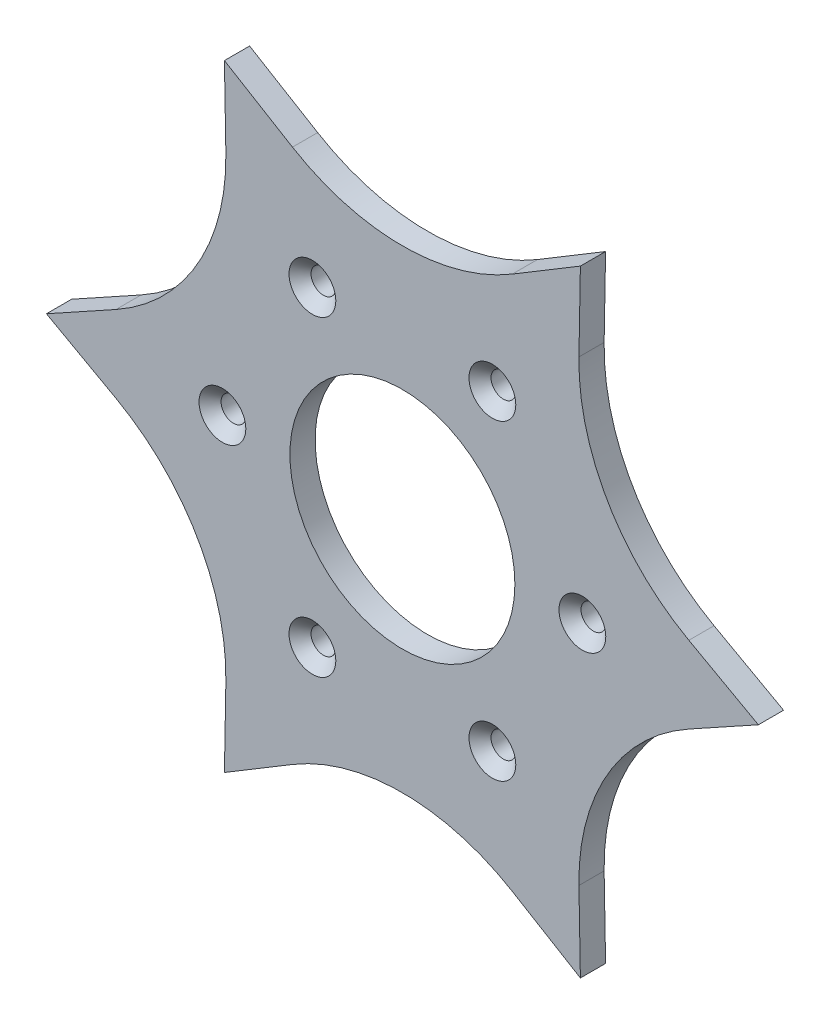
SolidWorks part; units mm, degrees
ref_plane "Front Plane" through (0, 0, 0) normal (0, 0, 1) x (1, 0, 0)
ref_plane "Top Plane" through (0, 0, 0) normal (0, 1, 0) x (1, 0, 0)
ref_plane "Right Plane" through (0, 0, 0) normal (1, 0, 0) x (0, 0, -1)
ref_plane "Plane1" through (0, 0, 62.5456) normal (0, 0, 1) x (1, 0, 0)
sketch "Sketch7" plane through (0, 0, 62.5456) normal (0, 0, 1) x (1, 0, 0)
  line L60 (-39.5574, -68.5154) -> (-24.4318, -59.4109)
  line L63 (39.5574, -68.5154) -> (24.4318, -59.4109)
  line L65 (-39.5574, -68.5154) -> (-39.2354, -50.864)
  line L66 (-79.1148, 0) -> (-63.6672, -8.5469)
  line L69 (-79.1148, 0) -> (-63.6672, 8.5469)
  line L70 (-39.5574, 68.5154) -> (-39.2354, 50.864)
  line L73 (-39.5574, 68.5154) -> (-24.4318, 59.4109)
  line L74 (39.5574, 68.5154) -> (24.4318, 59.4109)
  line L77 (39.5574, 68.5154) -> (39.2354, 50.864)
  line L78 (79.1148, 0) -> (63.6672, 8.5469)
  line L81 (79.1148, 0) -> (63.6672, -8.5469)
  line L82 (39.5574, -68.5154) -> (39.2354, -50.864)
  circle A1 centre (0, 0) radius 25
  circle A19 centre (0, 0) radius 47.9176 construction
  arc A32 (24.4318, -59.4109) -> (-24.4318, -59.4109) centre (0, -100) ccw
  arc A35 (-39.2354, -50.864) -> (-63.6672, -8.5469) centre (-86.6025, -50) ccw
  arc A37 (-63.6672, 8.5469) -> (-39.2354, 50.864) centre (-86.6025, 50) ccw
  arc A39 (-24.4318, 59.4109) -> (24.4318, 59.4109) centre (0, 100) ccw
  arc A41 (39.2354, 50.864) -> (63.6672, 8.5469) centre (86.6025, 50) ccw
  arc A43 (63.6672, -8.5469) -> (39.2354, -50.864) centre (86.6025, -50) ccw
  point P32 (0, 0)
  point P39 (-85.1007, 50.0037)
  point P40 (46.5, 100)
  point P41 (0, 100)
  point P42 (-41.6025, 50)
  point P43 (-40.1025, 50)
  point P45 (-86.6025, 50)
  point P46 (45, 100)
  point P51 (0, 100)
  point P136 (0, 0)
  point P183 (0, 0)
  dimension "D3" = 50
extrude "Boss-Extrude5" add sketch "Sketch7" along normal blind 5.6 separate body contours A1 region at (-37.3036, -59.7279, 62.5456)
sketch "Sketch8" plane through (0, 0, 68.1456) normal (0, 0, 1) x (1, 0, 0)
  line L0 (0, 0) -> (-119.3408, 0)
hole_wizard "CSK for M5 Flat Head Machine Screw1" positions "Sketch12" profile "Sketch11" countersink size "M5" standard "ANSI Metric" end condition through all
sketch "Sketch12" plane through (0, 0, 68.1456) normal (0, 0, 1) x (1, 0, 0)
  line L0 (0, 0) -> (-119.3408, 0) construction
  point P0 (-40, 0)
  dimension "D1" = 0
  dimension "D2" = 40
sketch "Sketch11" plane through (-40, 0, 68.1456) normal (1, 0, 0) x (0, -1, 0)
  line L0 (0, 0) -> (0, 5.6)
  line L1 (0, 5.6) -> (2.75, 5.6)
  line L2 (2.75, 5.6) -> (2.75, 2.45)
  line L3 (2.75, 2.45) -> (5.2, 0)
  line L5 (5.2, 0) -> (0, 0)
  line L6 (-2.75, 2.45) -> (-5.2, 0) construction
  line L11 (0, -6.35) -> (0, 107.95) construction
  dimension "Thru Hole Dia." = 5.5
  dimension "Thru Hole Depth" = 5.6
  dimension "Near C'Sink Dia." = 10.4
  dimension "Near C'Sink Angle" = 90
pattern_circular "CirPattern1" count 6 over 360 about axis through (0, 0, 68.1456) along (0, 0, 1) of "CSK for M5 Flat Head Machine Screw1"
